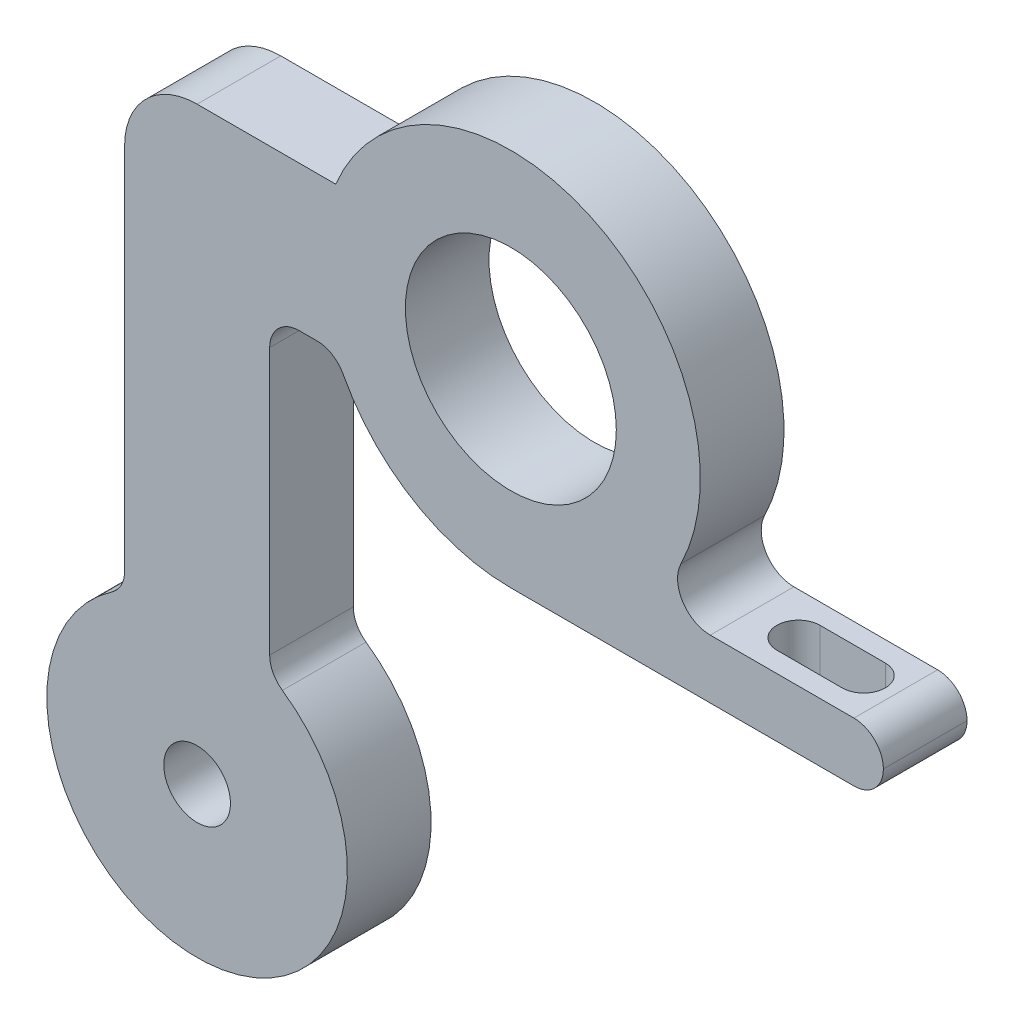
SolidWorks part; units mm, degrees
ref_plane "Front Plane" through (0, 0, 0) normal (0, 0, 1) x (1, 0, 0)
ref_plane "Top Plane" through (0, 0, 0) normal (0, 1, 0) x (1, 0, 0)
ref_plane "Right Plane" through (0, 0, 0) normal (1, 0, 0) x (0, 0, -1)
sketch "Sketch1" plane through (0, 0, 0) normal (0, 0, 1) x (1, 0, 0)
  line L0 (0, 0) -> (0, 39.5) construction
  line L1 (-5.55, 0) -> (-5.55, 39.5)
  line L2 (5.55, 0) -> (5.55, 39.5)
  line L3 (0, 39.5) -> (24, 39.5) construction
  line L4 (0, 45.05) -> (24, 45.05)
  line L5 (0, 33.95) -> (24, 33.95)
  line L6 (24, 25) -> (52.5, 25)
  line L7 (52.5, 25) -> (52.5, 29.5)
  line L8 (52.5, 29.5) -> (34.5, 29.5)
  line L9 (45.3, 29.5) -> (45.3, 25)
  line L10 (48.3, 29.5) -> (48.3, 25)
  line L11 (42.3, 29.5) -> (42.3, 25)
  line L12 (42.3, 27.25) -> (48.3, 27.25) construction
  circle A0 centre (0, 0) radius 2.55
  arc A1 (-5.55, 0) -> (5.55, 0) centre (0, 0) ccw
  arc A2 (5.55, 39.5) -> (-5.55, 39.5) centre (0, 39.5) ccw
  arc A3 (0, 45.05) -> (0, 33.95) centre (0, 39.5) ccw
  arc A4 (24, 33.95) -> (24, 45.05) centre (24, 39.5) ccw
  circle A5 centre (24, 39.5) radius 8.07
  circle A6 centre (24, 39.5) radius 14.5
  circle A7 centre (0, 0) radius 8
  circle A8 centre (0, 0) radius 11.5
  point P3 (0, 19.75)
  point P9 (12, 39.5)
  point P34 (45.3, 27.25)
  dimension "D1" = 5.1
  dimension "D5" = 16.14
  dimension "D6" = 29
  dimension "D7" = 16
  dimension "D8" = 23
  dimension "D2" = 3
  dimension "D3" = 39.5
  dimension "D4" = 24
  dimension "D9" = 4.5
  dimension "D10" = 21.3
  dimension "D11" = 18
  dimension "D12" = 6
extrude "Boss-Extrude3" add sketch "Sketch1" along normal blind 6.4 contours A3 L1 A1 L2 L5 A0 | A2 A3 L5 L2 | A6 L4 A2 L2 L5 | L4 A6 L5 A5 | L5 A6 L4 A5 | L1 A8 L2 A7 | L2 A8 L1 A7 | A6 L6 L11 L8 | L8 L11 L6 L9 | L10 L8 L9 L6 | L8 L10 L6 L7 | L1 A7 L2 A1 | L2 A7 L1 A1 A0 region at (0, -5.761, 0) region at (-5.3748, 2.8809, 0) region at (-3.2539, -7.6523, 0) region at (0, 9.1362, 0) region at (-0.1092, 22.8111, 0) region at (0.2756, 39.2244, 0) region at (7.305, 40.023, 0) region at (26.7509, 53.3266, 0) region at (13.2644, 39.5, 0) region at (36.5072, 26.972, 0) region at (43.8, 27.25, 0) region at (46.8, 27.25, 0) region at (50.4, 27.25, 0)
sketch "Sketch2" plane through (0, 29.5, 0) normal (0, 1, 0) x (1, 0, 0)
  line L0 (45.3, 0) -> (45.3, -6.4) construction
  line L2 (42.8, -3.2) -> (47.8, -3.2) construction
  line L3 (42.8, -1.55) -> (47.8, -1.55)
  line L4 (42.8, -4.85) -> (47.8, -4.85)
  line L5 (52.5, -6.4) -> (34.5, -6.4) construction
  arc A1 (42.8, -1.55) -> (42.8, -4.85) centre (42.8, -3.2) ccw
  arc A2 (47.8, -4.85) -> (47.8, -1.55) centre (47.8, -3.2) ccw
  point P7 (45.3, -3.2)
  dimension "D2" = 1.65
  dimension "D1" = 5
extrude "Cut-Extrude1" cut sketch "Sketch2" against normal blind 16
fillet "Fillet1" radius 2.5 1 edges at (34.5, 29.5, 3.2)
fillet "Fillet2" radius 2.25 6 edges at (10.6042, 33.95, 3.2) (-5.55, 10.0721, 3.2) (5.55, 10.0721, 3.2) (5.55, 33.95, 3.2) (52.5, 25, 3.2) (52.5, 29.5, 3.2)
